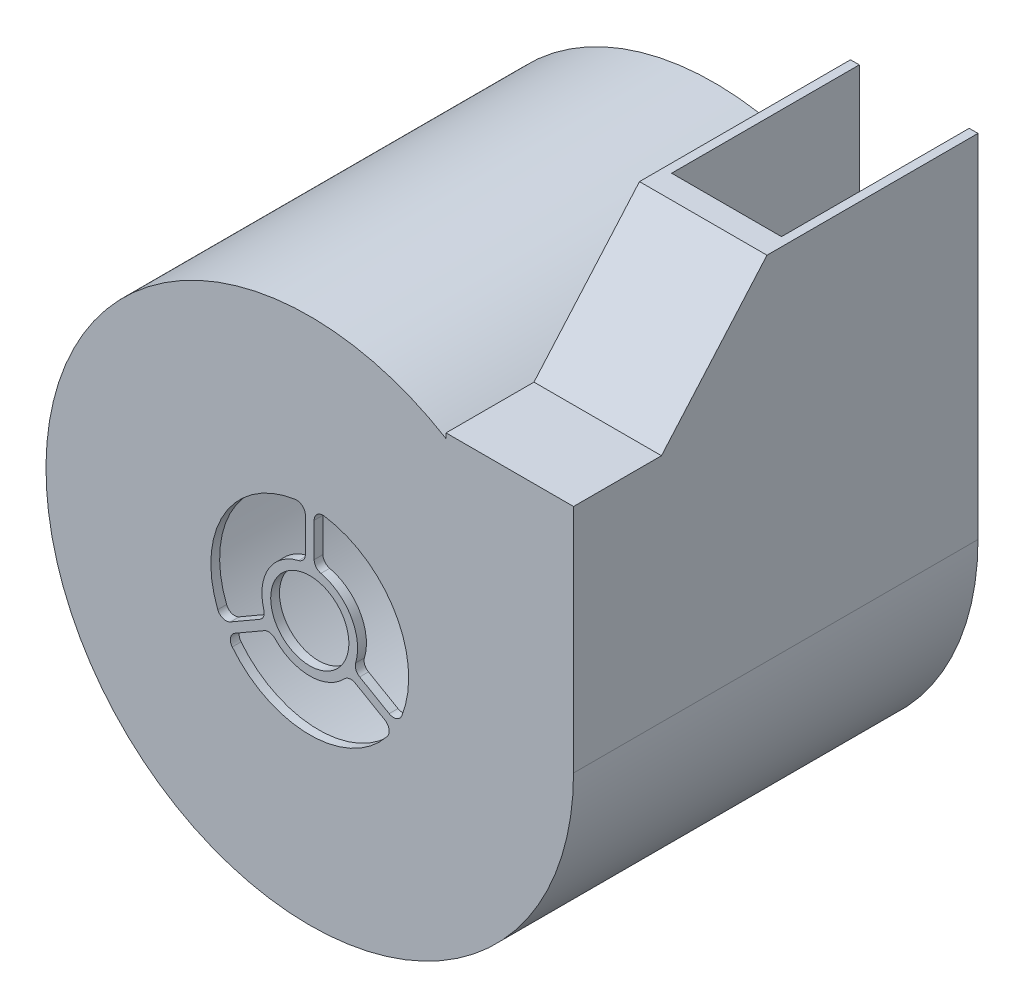
SolidWorks part; units mm, degrees
ref_plane "Front Plane" through (0, 0, 0) normal (0, 0, 1) x (1, 0, 0)
ref_plane "Top Plane" through (0, 0, 0) normal (0, 1, 0) x (1, 0, 0)
ref_plane "Right Plane" through (0, 0, 0) normal (1, 0, 0) x (0, 0, -1)
sketch "Sketch1" plane through (0, 0, 0) normal (0, 0, 1) x (1, 0, 0)
  circle A0 centre (0, 0) radius 600
  circle A1 centre (0, 0) radius 580
  dimension "D1" = 1200
  dimension "D2" = 20
extrude "Boss-Extrude1" add sketch "Sketch1" along normal mid plane 900
sketch "Sketch4" plane through (0, 0, 450) normal (0, 0, 1) x (1, 0, 0)
  circle A0 centre (0, 0) radius 600 construction
  circle A1 centre (0, 0) radius 600
extrude "Boss-Extrude2" add sketch "Sketch4" along normal blind 20
sketch "Sketch5" plane through (0, 0, 450) normal (0, 0, -1) x (-1, 0, 0)
  line L12 (10, 108.4287) -> (10, 224.7777)
  line L15 (-10, 108.4287) -> (-10, 224.7777)
  line L17 (-98.902, -45.5541) -> (-199.6632, -103.7286)
  line L18 (-88.902, -62.8746) -> (-189.6632, -121.0491)
  line L19 (88.902, -62.8746) -> (189.6632, -121.0491)
  line L22 (98.902, -45.5541) -> (199.6632, -103.7286)
  circle A0 centre (0, 0) radius 225
  circle A1 centre (0, 0) radius 88.8889
  arc A3 (-88.902, -62.8746) -> (88.902, -62.8746) centre (0, 0) ccw
  circle A4 centre (0, 0) radius 108.8889 construction
  arc A5 (-10, 108.4287) -> (-98.902, -45.5541) centre (0, 0) ccw
  arc A6 (98.902, -45.5541) -> (10, 108.4287) centre (0, 0) ccw
  point P11 (0, 0)
  point P12 (0, 0)
  dimension "D1" = 450
  dimension "D2" = 177.7778
  dimension "D3" = 20
sketch "Sketch7" plane through (0, 0, 0) normal (0, 1, 0) x (1, 0, 0)
  line L0 (600, 450) -> (580, 450) construction
  line L1 (580, 450) -> (-580, 450) construction
  line L3 (580, 450) -> (330, 450)
  line L4 (580, 450) -> (580, -450)
  line L5 (580, -450) -> (330, -450)
  line L6 (330, 450) -> (330, -450)
  dimension "D1" = 20
  dimension "D2" = 900
  dimension "D3" = 250
extrude "Cut-Extrude2" cut sketch "Sketch7" along normal through all
sketch "Sketch8" plane through (0, 0, 0) normal (0, 1, 0) x (1, 0, 0)
  line L0 (580, -450) -> (580, 450) construction
  line L1 (310, 450) -> (310, -470)
  line L2 (600, -470) -> (310, -470)
  line L3 (600, -470) -> (600, 450)
  line L4 (600, 450) -> (580, 450)
  line L5 (330, 450) -> (310, 450)
  line L7 (580, -450) -> (330, -450) construction
  line L8 (330, 450) -> (330, -450) construction
  line L9 (580, -450) -> (580, 450)
  line L10 (580, -450) -> (330, -450)
  line L11 (330, 450) -> (330, -450)
  dimension "D1" = 20
extrude "Boss-Extrude4" add sketch "Sketch8" along normal blind 800
sketch "Sketch10" plane through (580, 0, 0) normal (-1, 0, 0) x (0, 0, 1)
  line L0 (-450, 800) -> (450, 800) construction
  line L1 (-23.0461, 800) -> (350, 0)
  line L2 (350, 0) -> (450, 0)
  line L3 (470, 0) -> (-450, 0) construction
  line L4 (450, 0) -> (450, 800)
  line L5 (470, 800) -> (-450, 800) construction
  line L6 (450, 800) -> (-23.0461, 800)
  line L7 (470, 800) -> (470, 0) construction
  dimension "D1" = 20
  dimension "D2" = 100
  dimension "D3" = 25
extrude "Boss-Extrude5" add sketch "Sketch10" along normal up to next
sketch "Sketch11" plane through (0, 0, 0) normal (0, 0, 1) x (1, 0, 0)
  circle A0 centre (0, 0) radius 580 construction
  circle A1 centre (0, 0) radius 580
extrude "Cut-Extrude3" cut sketch "Sketch11" against normal through all
extrude "Cut-Extrude4" cut sketch "Sketch11<2>" along normal blind 450
sketch "Sketch11<2>" plane through (0, 0, 0) normal (0, 0, 1) x (1, 0, 0) same geometry as "Sketch11"
fillet "Fillet1" radius 50 1 edges at (513.712, 269.2582, 224.4428) tangent propagation no
sketch "Sketch12" plane through (310, 0, 0) normal (-1, 0, 0) x (0, 0, 1)
  line L0 (30, 800) -> (270, 525)
  line L1 (-450, 800) -> (470, 800) construction
  line L2 (270, 525) -> (470, 525)
  line L3 (470, 800) -> (470, 513.712) construction
  line L4 (470, 525) -> (470, 800)
  line L5 (470, 800) -> (470, 0) construction
  line L6 (470, 800) -> (30, 800)
  dimension "D1" = 440
  dimension "D2" = 200
  dimension "D3" = 275
extrude "Cut-Extrude5" cut sketch "Sketch12" against normal through all
extrude "Cut-Extrude6" cut sketch "Sketch5" against normal through all contours A6 L22 A0 L12 | A5 L15 A0 L17 | A3 L18 A0 L19 | A1 region at (-127.3231, 73.5101, 450) region at (127.3231, 73.5101, 450) region at (0, -147.0201, 450) region at (0, 0, 450)
ref_plane "Plane1" through (0, 0, -390) normal (0, 0, -1) x (-1, 0, 0)
sketch "Sketch13" plane through (0, 0, -390) normal (0, 0, -1) x (-1, 0, 0)
  line L4 (100.269, -80.9844) -> (491.996, -307.148)
  line L7 (-120.269, -46.3433) -> (-511.996, -272.507)
  line L10 (-100.269, -80.9844) -> (-491.996, -307.148)
  line L24 (20, 127.3277) -> (20, 579.6551)
  line L25 (-20, 127.3277) -> (-20, 579.6551)
  line L26 (120.269, -46.3433) -> (511.996, -272.507)
  circle A0 centre (0, 0) radius 88.8889 construction
  circle A1 centre (0, 0) radius 88.8889
  arc A3 (-100.269, -80.9844) -> (100.269, -80.9844) centre (0, 0) ccw
  arc A7 (120.269, -46.3433) -> (20, 127.3277) centre (0, 0) ccw
  circle A10 centre (0, 0) radius 580 construction
  arc A11 (-511.996, -272.507) -> (-491.996, -307.148) centre (0, 0) ccw
  arc A12 (20, 579.6551) -> (-20, 579.6551) centre (0, 0) ccw
  arc A13 (491.996, -307.148) -> (511.996, -272.507) centre (0, 0) ccw
  circle A14 centre (0, 0) radius 128.8889 construction
  arc A15 (-20, 127.3277) -> (-120.269, -46.3433) centre (0, 0) ccw
  point P8 (0, 0)
  point P13 (0, 0)
  dimension "D1" = 40
extrude "Boss-Extrude6" add sketch "Sketch13" against normal blind 20
fillet "Fillet2" radius 20 18 edges at (10, 224.7777, 460) (-10, 224.7777, 460) (199.6632, -103.7286, 460) (189.6632, -121.0491, 460) (-189.6632, -121.0491, 460) (-199.6632, -103.7286, 460) (-511.996, -272.507, -380) (-502.2947, -290, -370) (-491.996, -307.148, -380) (-502.2947, -290, -390) (511.996, -272.507, -380) (502.2947, -290, -370) (491.996, -307.148, -380) (502.2947, -290, -390) (20, 579.6551, -380) (0, 580, -370) (0, 580, -390) (-20, 579.6551, -380)
fillet "Fillet3" radius 20 12 edges at (100.269, -80.9844, -380) (120.269, -46.3433, -380) (20, 127.3277, -380) (-20, 127.3277, -380) (-100.269, -80.9844, -380) (-120.269, -46.3433, -380) (98.902, -45.5541, 460) (10, 108.4287, 460) (-10, 108.4287, 460) (-98.902, -45.5541, 460) (-88.902, -62.8746, 460) (88.902, -62.8746, 460)
fillet "Fillet5" radius 40 1 edges at (580, 0, 450)
